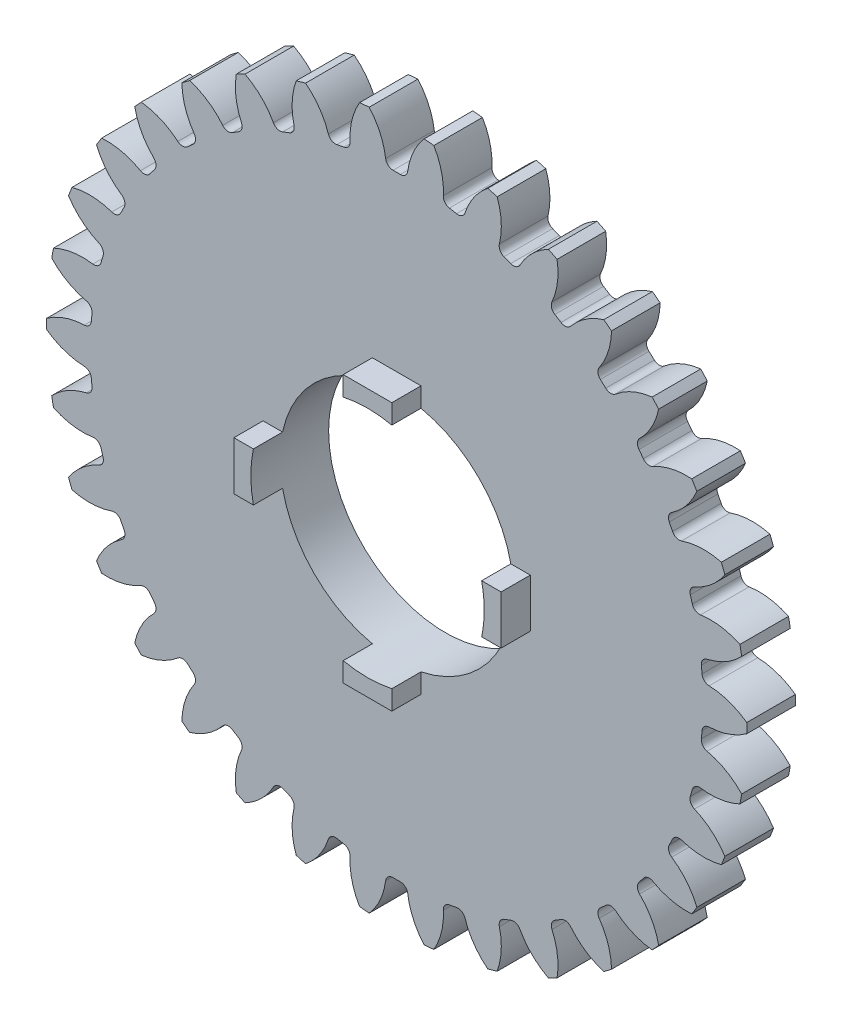
SolidWorks part; units mm, degrees
ref_plane "Front Plane" through (0, 0, 0) normal (0, 0, 1) x (1, 0, 0)
ref_plane "Top Plane" through (0, 0, 0) normal (0, 1, 0) x (1, 0, 0)
ref_plane "Right Plane" through (0, 0, 0) normal (1, 0, 0) x (0, 0, -1)
sketch "Sketch1" plane through (0, 0, 0) normal (0, 0, 1) x (1, 0, 0)
  line L4 (-1.0789, 31.4815) -> (0, 0) construction
  line L5 (0, 0) -> (0, 36) construction
  line L6 (0, 0) -> (3.3217, 35.8464) construction
  line L7 (-1.6208, 33.9613) -> (0.7854, 34.9695) construction
  line L8 (-1.6208, 33.9613) -> (0.4021, 34.0579) construction
  line L11 (1.6208, 33.9613) -> (-1.6208, 33.9613) construction
  circle A0 centre (0, 0) radius 31.5
  circle A1 centre (0, 0) radius 34 construction
  circle A2 centre (0, 0) radius 36
  arc A3 (-2.8235, 35.8891) -> (-1.0789, 31.4815) centre (-8.1293, 31.2399) cw
  arc A4 (2.8235, 35.8891) -> (1.0789, 31.4815) centre (8.1293, 31.2399) ccw
  point P5 (-34, 0)
  point P6 (-36, 0)
  point P7 (-31.5, 0)
  point P12 (-1.6208, 33.9613)
  point P22 (1.6208, 33.9613)
  dimension "D5" = 68
  dimension "D1" = 2.5
  dimension "D2" = 2
  dimension "D3" = 20
  dimension "D4" = 3.2416
  dimension "D6" = 5.294
  dimension "D7" = 0.5
extrude "Boss-Extrude1" add sketch "Sketch1" against normal blind 5 contours A2
extrude "Cut-Extrude1" cut sketch "Sketch1<4>" against normal blind 10 contours A4 A2 A3 A0 region at (0, 34.1183, 0)
sketch "Sketch1<4>" plane through (0, 0, 0) normal (0, 0, 1) x (1, 0, 0) same geometry as "Sketch1"
fillet "Fillet2" radius 0.76 2 edges at (1.0789, 31.4815, -2.5) (-1.0789, 31.4815, -2.5)
ref_axis "Axis1" through (0, 0, 0) along (0, 0, 1)
pattern_circular "CirPattern2" count 34 over 360 about axis through (0, 0, 0) along (0, 0, 1) of "Cut-Extrude1", "Fillet2"
sketch "Sketch2" plane through (0, 0, 0) normal (0, 0, 1) x (1, 0, 0)
  circle A0 centre (0, 0) radius 12
  dimension "D1" = 24
extrude "Cut-Extrude2" cut sketch "Sketch2" against normal up to surface (5 mm away) up to face at (0, 0, -5)
sketch "Sketch3" plane through (0, 0, 0) normal (0, 0, 1) x (1, 0, 0)
  line L0 (-2.5, 11.7367) -> (-2.5, 13.7367)
  line L1 (-2.5, 13.7367) -> (2.5, 13.7367)
  line L2 (2.5, 13.7367) -> (2.5, 11.7367)
  line L3 (0, 0) -> (0, 12) construction
  line L4 (13.7367, -2.5) -> (11.7367, -2.5)
  line L5 (13.7367, 2.5) -> (13.7367, -2.5)
  line L6 (11.7367, 2.5) -> (13.7367, 2.5)
  line L7 (-2.5, -13.7367) -> (-2.5, -11.7367)
  line L8 (2.5, -13.7367) -> (-2.5, -13.7367)
  line L9 (2.5, -11.7367) -> (2.5, -13.7367)
  line L10 (-13.7367, 2.5) -> (-11.7367, 2.5)
  line L11 (-13.7367, -2.5) -> (-13.7367, 2.5)
  line L12 (-11.7367, -2.5) -> (-13.7367, -2.5)
  circle A0 centre (0, 0) radius 12 construction
  arc A1 (-2.5, 11.7367) -> (2.5, 11.7367) centre (0, 0) cw
  arc A2 (11.7367, 2.5) -> (11.7367, -2.5) centre (0, 0) cw
  arc A3 (2.5, -11.7367) -> (-2.5, -11.7367) centre (0, 0) cw
  arc A4 (-11.7367, -2.5) -> (-11.7367, 2.5) centre (0, 0) cw
  point P24 (0, 0)
  dimension "D4" = 4
  dimension "D1" = 2.5
  dimension "D2" = 2.5
  dimension "D3" = 2
extrude "Boss-Extrude2" add sketch "Sketch3" along normal blind 3
equation "\"backlash\"= 0.1mm"
equation "\"module\"= 2mm"
equation "\"pressureAngle\"= 20deg"
equation "\"width\"= 10mm"
equation "\"D1@Sketch1\"= 1.25 * \"module\""
equation "\"D2@Sketch1\"=\"module\""
equation "\"D5@Sketch1\"=\"module\"*\"numberOfTeeth\""
equation "\"D1@Boss-Extrude1\"=\"width\"-5"
equation "\"D3@Sketch1\"=\"pressureAngle\""
equation "\"D1@Cut-Extrude1\"=\"width\""
equation "\"D1@CirPattern2\"=\"numberOfTeeth\""
equation "\"D1@Fillet2\"=0.38*\"module\""
equation "\"D4@Sketch1\"=pi*\"module\"/2+\"backlash\""
equation "\"numberOfTeeth\"= 34"
equation "\"D6@Sketch1\"=180/\"numberOfTeeth\""
equation "\"toothTipProfile\"= 1mm"
equation "\"D7@Sketch1\"=\"toothTipProfile\"/2"
equation "\"lengthOverallRack\"= pi * \"module\" * \"numberOfTeethRack\""
equation "\"numberOfTeethRack\"= 20"
